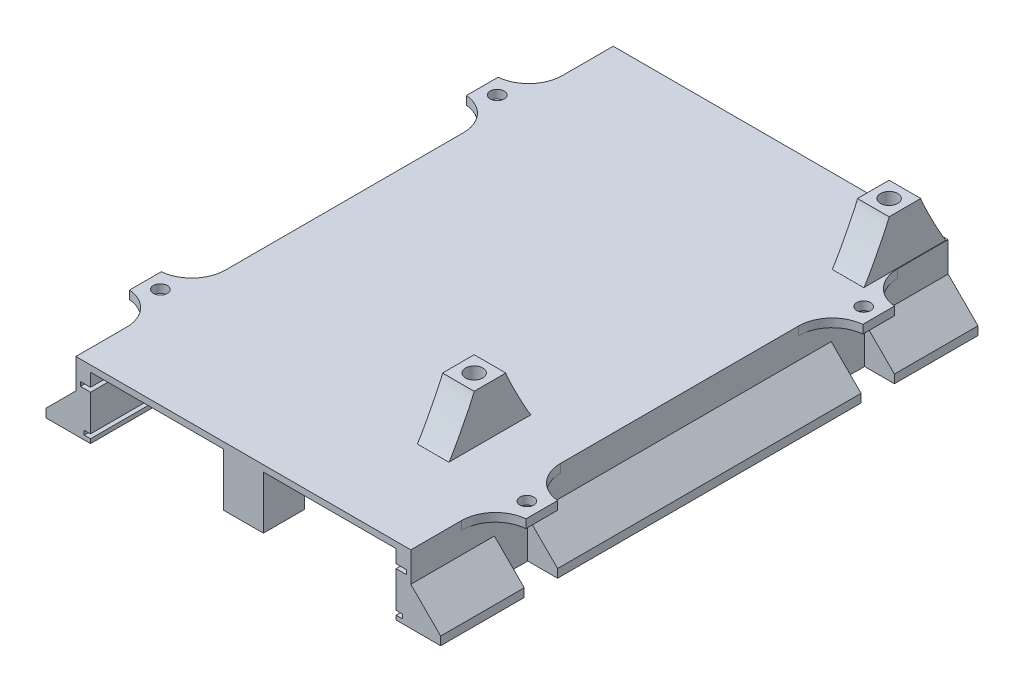
SolidWorks part; units mm, degrees
material "PLA"
ref_plane "Спереди" through (0, 0, 0) normal (0, 0, 1) x (1, 0, 0)
ref_plane "Сверху" through (0, 0, 0) normal (0, 1, 0) x (1, 0, 0)
ref_plane "Справа" through (0, 0, 0) normal (1, 0, 0) x (0, 0, -1)
sketch "Эскиз1" plane through (0, 0, 0) normal (0, 1, 0) x (1, 0, 0)
  line L0 (0, 0) -> (-4740.9496, 0) construction
  line L1 (0, 0) -> (0, -4740.9496) construction
  line L2 (36.2, 63.65) -> (39.675, 63.65)
  line L3 (-36.2, -63.65) -> (-39.675, -63.65)
  line L4 (-36.2, -63.65) -> (-36.2, 63.65)
  line L5 (-36.2, 63.65) -> (-39.675, 63.65)
  line L6 (-39.675, -63.65) -> (-39.675, 63.65)
  line L7 (-36.2, -63.65) -> (-39.675, 63.65) construction
  line L8 (-36.2, 63.65) -> (-39.675, -63.65) construction
  line L9 (39.675, -63.65) -> (39.675, 63.65)
  line L10 (36.2, -63.65) -> (39.675, -63.65)
  line L11 (36.2, -63.65) -> (36.2, 63.65)
  line L12 (36.2, 63.65) -> (39.675, -63.65) construction
  line L13 (36.2, -63.65) -> (39.675, 63.65) construction
  point P5 (-37.9375, 0)
  point P14 (37.9375, 0)
  dimension "D2" = 127.3
  dimension "D3" = 72.4
  dimension "D4" = 79.35
extrude "Бобышка-Вытянуть1" add sketch "Эскиз1" along normal blind 12.65
sketch "Эскиз2" plane through (0, 12.65, 0) normal (0, 1, 0) x (1, 0, 0)
  line L1 (39.675, 63.65) -> (-39.675, 63.65)
  line L2 (39.675, 63.65) -> (39.675, -63.65)
  line L3 (39.675, -63.65) -> (-39.675, -63.65)
  line L4 (-39.675, 63.65) -> (-39.675, -63.65)
extrude "Бобышка-Вытянуть2" add sketch "Эскиз2" along normal blind 1.5
sketch "Эскиз3" plane through (0, 0, -63.65) normal (0, 0, -1) x (-1, 0, 0)
  line L0 (0, 0) -> (0, 50000) construction
  line L1 (-36.2, 12.65) -> (-36.2, 0) construction
  line L2 (-36.2, 9.55) -> (-38.6, 9.55)
  line L3 (-36.2, 9.55) -> (-36.2, 8.55)
  line L4 (-36.2, 8.55) -> (-38.6, 8.55)
  line L5 (-38.6, 9.55) -> (-38.6, 8.55)
  line L6 (36.2, 8.55) -> (38.6, 8.55)
  line L7 (38.6, 9.55) -> (38.6, 8.55)
  line L8 (36.2, 9.55) -> (38.6, 9.55)
  line L9 (36.2, 9.55) -> (36.2, 8.55)
  line L10 (-39.675, 0) -> (-36.2, 0) construction
  dimension "D1" = 2.4
  dimension "D2" = 1
  dimension "D3" = 8.55
extrude "Вырез-Вытянуть1" cut sketch "Эскиз3" against normal through all from offset 1.5 offset against normal yes
sketch "Эскиз4" plane through (0, 12.65, 0) normal (0, -1, 0) x (1, 0, 0)
  line L0 (36.2, -63.65) -> (36.2, 63.65) construction
  line L1 (-36.2, -63.65) -> (36.2, -63.65)
  line L2 (-36.2, -63.65) -> (-36.2, -62.15)
  line L3 (-36.2, -62.15) -> (36.2, -62.15)
  line L4 (36.2, -63.65) -> (36.2, -62.15)
  dimension "D1" = 1.5
extrude "Бобышка-Вытянуть3" add sketch "Эскиз4" along normal up to surface (12.65 mm away) up to face at (37.9375, 0, 0)
sketch "Эскиз6" plane through (0, 12.65, 0) normal (0, -1, 0) x (1, 0, 0)
  line L0 (36.2, -62.15) -> (36.2, 63.65) construction
  line L1 (32.85, -52.35) -> (25.35, -52.35)
  line L2 (32.85, -52.35) -> (32.85, -62.15)
  line L3 (32.85, -59.85) -> (25.35, -59.85) construction
  line L4 (25.35, -52.35) -> (25.35, -62.15)
  line L5 (32.85, -52.35) -> (25.35, -59.85) construction
  line L6 (32.85, -59.85) -> (25.35, -52.35) construction
  line L7 (36.2, -62.15) -> (-36.2, -62.15) construction
  line L8 (32.85, -62.15) -> (25.35, -62.15)
  circle A0 centre (29.1, -56.1) radius 2.1 construction
  point P0 (29.1, -56.1)
  dimension "D3" = 4.2
  dimension "D4" = 1.65
  dimension "D5" = 1.65
  dimension "D1" = 7.1
  dimension "D2" = 6.05
extrude "Бобышка-Вытянуть5" add sketch "Эскиз6" along normal blind 9.6
sketch "Эскиз7" plane through (0, 3.05, 0) normal (0, -1, 0) x (1, 0, 0)
  line L0 (25.35, -52.35) -> (32.85, -59.85) construction
  line L1 (32.85, -52.35) -> (25.35, -59.85) construction
  line L2 (32.85, -62.15) -> (32.85, -52.35) construction
  line L3 (25.35, -52.35) -> (25.35, -62.15) construction
  circle A0 centre (29.1, -56.1) radius 2.05
  dimension "D1" = 4.1
extrude "Вырез-Вытянуть2" cut sketch "Эскиз7" against normal blind 4.5
sketch "Эскиз8" plane through (0, 0, 0) normal (0, -1, 0) x (1, 0, 0)
  line L0 (-36.2, 63.65) -> (-36.2, -62.15) construction
  line L1 (-36.2, 36.4) -> (-38.6, 36.4)
  line L2 (-36.2, 36.4) -> (-36.2, 30.55)
  line L3 (-36.2, 30.55) -> (-38.6, 30.55)
  line L4 (-38.6, 36.4) -> (-38.6, 30.55)
  line L5 (0, 0) -> (0, 50000) construction
  line L6 (-36.2, -18.2) -> (-38.6, -18.2)
  line L7 (-36.2, -18.2) -> (-36.2, -24.05)
  line L8 (-36.2, -24.05) -> (-38.6, -24.05)
  line L9 (-38.6, -18.2) -> (-38.6, -24.05)
  line L10 (-39.675, 63.65) -> (-36.2, 63.65) construction
  line L11 (36.2, -24.05) -> (38.6, -24.05)
  line L12 (38.6, -18.2) -> (38.6, -24.05)
  line L13 (36.2, -18.2) -> (38.6, -18.2)
  line L14 (36.2, -18.2) -> (36.2, -24.05)
  line L15 (36.2, 30.55) -> (38.6, 30.55)
  line L16 (38.6, 36.4) -> (38.6, 30.55)
  line L17 (36.2, 36.4) -> (38.6, 36.4)
  line L18 (36.2, 36.4) -> (36.2, 30.55)
  line L19 (39.675, -63.65) -> (-39.675, -63.65) construction
  point P26 (0, -63.65)
  dimension "D1" = 2.4
  dimension "D2" = 5.85
  dimension "D3" = 48.75
  dimension "D4" = 27.25
extrude "Вырез-Вытянуть3" cut sketch "Эскиз8" against normal up to surface (8.55 mm away) up to face at (-37.4, 8.55, 0.75)
sketch "Эскиз10" plane through (0, 12.65, 0) normal (0, -1, 0) x (1, 0, 0)
  line L0 (-36.2, 63.65) -> (-36.2, -62.15) construction
  line L1 (-25.8, -51.75) -> (-28.8, -51.75)
  line L2 (-25.8, -51.75) -> (-25.8, -57.7)
  line L3 (-25.8, -57.7) -> (-28.8, -57.7)
  line L4 (-28.8, -51.75) -> (-28.8, -57.7)
  line L5 (25.35, -62.15) -> (-36.2, -62.15) construction
  line L6 (36.2, -62.15) -> (-36.2, -62.15) construction
  line L8 (14.7, -51.75) -> (17.7, -51.75)
  line L9 (14.7, -51.75) -> (14.7, -57.7)
  line L10 (14.7, -57.7) -> (17.7, -57.7)
  line L11 (17.7, -51.75) -> (17.7, -57.7)
  dimension "D1" = 10.4
  dimension "D2" = 4.45
  dimension "D3" = 10.4
  dimension "D4" = 3
  dimension "D5" = 50.9
extrude "Бобышка-Вытянуть6" add sketch "Эскиз10" along normal blind 3.95
sketch "Эскиз11" plane through (0, 12.65, 0) normal (0, -1, 0) x (1, 0, 0)
  line L1 (-25.8, -57.7) -> (14.7, -57.7)
  line L2 (-25.8, -57.7) -> (-25.8, -51.75)
  line L3 (-25.8, -51.75) -> (14.7, -51.75)
  line L4 (14.7, -57.7) -> (14.7, -51.75)
extrude "Бобышка-Вытянуть7" add sketch "Эскиз11" along normal blind 0.35
fillet "Скругление4" radius 4 1 edges at (-5.55, 12.65, -57.7)
fillet "Скругление5" radius 2 2 edges at (-27.3, 8.7, -57.7) (16.2, 8.7, -57.7)
sketch "Эскиз12" plane through (0, 0, -62.15) normal (0, 0, 1) x (1, 0, 0)
  line L1 (15.95, 6.65) -> (-27.05, 6.65)
  line L2 (15.95, 6.65) -> (15.95, 11.65)
  line L7 (25.35, 12.65) -> (-36.2, 12.65) construction
  line L12 (15.95, 11.65) -> (-27.05, 11.65)
  line L13 (-27.05, 6.65) -> (-27.05, 11.65)
  line L15 (-5.55, 12.3) -> (-5.55, 11.65) construction
  line L17 (-25.8, 12.3) -> (14.7, 12.3) construction
  point P13 (-5.55, 12.3)
  dimension "D1" = 5
  dimension "D2" = 43
  dimension "D3" = 1
extrude "Вырез-Вытянуть4" cut sketch "Эскиз12" against normal through all
sketch "Эскиз13" plane through (0, 12.65, 0) normal (0, -1, 0) x (1, 0, 0)
  line L0 (0, 63.65) -> (0, 50063.65) construction
  line L1 (-36.2, 63.65) -> (36.2, 63.65) construction
  line L2 (-4.75, 63.4) -> (-4.75, 63.65)
  line L3 (4.75, 63.4) -> (-4.75, 63.4) construction
  line L4 (4.75, 63.4) -> (4.75, 53.9)
  line L5 (4.75, 53.9) -> (-4.75, 53.9)
  line L6 (-4.75, 63.4) -> (-4.75, 53.9)
  line L7 (4.75, 63.4) -> (-4.75, 53.9) construction
  line L8 (4.75, 53.9) -> (-4.75, 63.4) construction
  line L9 (-4.75, 63.65) -> (4.75, 63.65)
  line L10 (4.75, 63.65) -> (4.75, 63.4)
  circle A0 centre (0, 58.65) radius 2.75 construction
  point P4 (0, 63.65)
  point P5 (0, 58.65)
  dimension "D1" = 5.5
  dimension "D2" = 9.5
  dimension "D3" = 5
  dimension "D4" = 0.25
extrude "Бобышка-Вытянуть8" add sketch "Эскиз13" along normal blind 12.55
sketch "Эскиз14" plane through (0, 0.1, 0) normal (0, -1, 0) x (1, 0, 0)
  line L0 (-4.75, 63.4) -> (4.75, 53.9) construction
  line L1 (4.75, 63.4) -> (-4.75, 53.9) construction
  line L2 (4.75, 53.9) -> (4.75, 63.65) construction
  line L3 (-4.75, 63.65) -> (-4.75, 53.9) construction
  line L4 (-4.75, 63.4) -> (4.75, 63.4) construction
  circle A0 centre (0, 58.65) radius 2.05
  dimension "D1" = 4.1
extrude "Вырез-Вытянуть5" cut sketch "Эскиз14" against normal blind 7
sketch "Эскиз15" plane through (0, 14.15, 0) normal (0, 1, 0) x (1, 0, 0)
  line L0 (39.675, -63.65) -> (39.675, 63.65) construction
  line L1 (32.0454, 57.2971) -> (39.5454, 57.2971)
  line L2 (32.0454, 57.2971) -> (32.0454, 49.7971)
  line L3 (32.0454, 49.7971) -> (39.5454, 49.7971)
  line L4 (39.5454, 57.2971) -> (39.5454, 49.7971)
  line L5 (32.0454, 57.2971) -> (39.5454, 49.7971) construction
  line L6 (32.0454, 49.7971) -> (39.5454, 57.2971) construction
  line L7 (18.7005, -27.6612) -> (26.2005, -27.6612)
  line L8 (18.7005, -27.6612) -> (18.7005, -35.1612)
  line L9 (18.7005, -35.1612) -> (26.2005, -35.1612)
  line L10 (26.2005, -27.6612) -> (26.2005, -35.1612)
  line L11 (18.7005, -27.6612) -> (26.2005, -35.1612) construction
  line L12 (18.7005, -35.1612) -> (26.2005, -27.6612) construction
  line L13 (-39.675, -63.65) -> (39.675, -63.65) construction
  point P0 (35.7954, 53.5471)
  point P5 (22.4505, -31.4112)
  dimension "D1" = 7.5
  dimension "D2" = 17.2245
  dimension "D3" = 32.2388
  dimension "D4" = 3.8796
  dimension "D5" = 117.1971
extrude "Бобышка-Вытянуть9" add sketch "Эскиз15" along normal blind 11.55
sketch "Эскиз16" plane through (0, 25.7, 0) normal (0, 1, 0) x (1, 0, 0)
  line L0 (32.0454, 57.2971) -> (39.5454, 49.7971) construction
  line L1 (39.5454, 57.2971) -> (32.0454, 49.7971) construction
  line L2 (26.2005, -27.6612) -> (18.7005, -35.1612) construction
  line L3 (18.7005, -27.6612) -> (26.2005, -35.1612) construction
  circle A0 centre (22.4505, -31.4112) radius 2.05
  circle A1 centre (35.7954, 53.5471) radius 2.05
  dimension "D1" = 4.1
extrude "Вырез-Вытянуть6" cut sketch "Эскиз16" against normal blind 5
sketch "Эскиз17" plane through (0, 0, -63.65) normal (0, 0, -1) x (-1, 0, 0)
  line L0 (-39.675, 7.075) -> (-46.75, 0)
  line L1 (-39.675, 14.15) -> (-39.675, 0) construction
  line L2 (-46.75, 0) -> (-39.675, 0)
  line L3 (-39.675, 0) -> (-39.675, 7.075)
  line L4 (0, 0) -> (0, 50000) construction
  line L5 (46.75, 0) -> (39.675, 0)
  line L6 (39.675, 7.075) -> (46.75, 0)
  line L7 (39.675, 0) -> (39.675, 7.075)
extrude "Бобышка-Вытянуть10" add sketch "Эскиз17" against normal up to surface (127.3 mm away) up to face at (0, 7.575, 63.65)
sketch "Эскиз18" plane through (0, 0, -63.65) normal (0, 0, -1) x (-1, 0, 0)
  line L0 (-46.75, 0) -> (-46.75, -2)
  line L1 (-46.75, -2) -> (-36.2, -2)
  line L2 (-36.2, -2) -> (-36.2, -1)
  line L3 (-36.2, -1) -> (-37.7, -1)
  line L4 (-37.7, -1) -> (-37.7, 0)
  line L5 (-46.75, 0) -> (46.75, 0) construction
  line L6 (-37.7, 0) -> (-46.75, 0)
  line L7 (-36.2, 8.55) -> (-36.2, 0) construction
  line L8 (0, 0) -> (0, 50000) construction
  line L9 (37.7, -1) -> (37.7, 0)
  line L10 (36.2, -1) -> (37.7, -1)
  line L11 (36.2, -2) -> (36.2, -1)
  line L12 (46.75, -2) -> (36.2, -2)
  line L13 (46.75, 0) -> (46.75, -2)
  line L14 (37.7, 0) -> (46.75, 0)
  point P21 (0, 0)
  dimension "D1" = 2
  dimension "D2" = 1
  dimension "D3" = 1.5
extrude "Бобышка-Вытянуть11" add sketch "Эскиз18" against normal up to surface (127.3 mm away) up to face at (0, 7.5295, 63.65)
sketch "Эскиз19" plane through (0, 14.15, 0) normal (0, 1, 0) x (1, 0, 0)
  line L0 (-39.675, -63.65) -> (-46.75, -63.65) construction
  line L1 (-49.0446, -29.2779) -> (-41.5446, -29.2779) construction
  line L2 (-49.0446, -29.2779) -> (-49.0446, -21.7779) construction
  line L3 (-49.0446, -21.7779) -> (-41.5446, -21.7779) construction
  line L4 (-41.5446, -29.2779) -> (-41.5446, -21.7779) construction
  line L5 (-39.675, 63.65) -> (-39.675, -63.65) construction
  line L6 (-49.2446, -29.4779) -> (-41.3446, -29.4779)
  line L7 (-41.3446, -29.4779) -> (-41.3446, -21.5779)
  line L8 (-49.2446, -21.5779) -> (-41.3446, -21.5779)
  line L9 (-49.2446, -29.4779) -> (-49.2446, -21.5779)
  dimension "D1" = 34.3721
  dimension "D2" = 7.5
  dimension "D3" = 1.8696
  dimension "D4" = 0.2
extrude "Вырез-Вытянуть7" cut sketch "Эскиз19" against normal up to surface (16.15 mm away) up to face at (-41.475, -2, 0)
sketch "Эскиз20" plane through (0, -2, 0) normal (0, -1, 0) x (1, 0, 0)
  line L0 (0, 0) -> (0, 50000) construction
  line L1 (0, 0) -> (50000, 0) construction
  line L3 (39.875, 43.65) -> (47.375, 43.65) construction
  line L4 (39.875, 43.65) -> (39.875, 36.15) construction
  line L5 (39.875, 36.15) -> (47.375, 36.15) construction
  line L6 (47.375, 43.65) -> (47.375, 36.15) construction
  line L7 (36.2, 63.65) -> (46.75, 63.65) construction
  line L20 (39.675, 43.85) -> (47.575, 43.85)
  line L21 (47.575, 43.85) -> (47.575, 35.95)
  line L22 (39.675, 35.95) -> (47.575, 35.95)
  line L23 (39.675, 43.85) -> (39.675, 35.95)
  line L24 (39.675, -43.85) -> (39.675, -35.95)
  line L25 (39.675, -35.95) -> (47.575, -35.95)
  line L26 (47.575, -43.85) -> (47.575, -35.95)
  line L27 (39.675, -43.85) -> (47.575, -43.85)
  line L28 (-39.675, -43.85) -> (-47.575, -43.85)
  line L29 (-47.575, -43.85) -> (-47.575, -35.95)
  line L30 (-39.675, -35.95) -> (-47.575, -35.95)
  line L31 (-39.675, -43.85) -> (-39.675, -35.95)
  line L32 (-39.675, 43.85) -> (-39.675, 35.95)
  line L33 (-39.675, 35.95) -> (-47.575, 35.95)
  line L34 (-47.575, 43.85) -> (-47.575, 35.95)
  line L35 (-39.675, 43.85) -> (-47.575, 43.85)
  line L38 (39.675, 63.65) -> (39.675, -63.65) construction
  dimension "D1" = 7.5
  dimension "D2" = 20
  dimension "D3" = 0.2
extrude "Вырез-Вытянуть8" cut sketch "Эскиз20" against normal through all
sketch "Эскиз21" plane through (0, 14.15, 0) normal (0, 1, 0) x (1, 0, 0)
  line L0 (0, 0) -> (-50000, 0) construction
  line L1 (0, 0) -> (0, 50000) construction
  line L2 (39.675, -63.65) -> (39.675, 63.65) construction
  line L3 (39.675, 43.65) -> (46.95, 43.65)
  line L4 (39.675, 43.65) -> (39.675, 36.15)
  line L5 (39.675, 36.15) -> (46.95, 36.15)
  line L6 (46.95, 43.65) -> (46.95, 36.15)
  line L7 (46.75, 43.85) -> (39.675, 43.85) construction
  line L8 (39.675, 35.95) -> (46.75, 35.95) construction
  line L10 (39.675, -36.15) -> (46.95, -36.15)
  line L11 (46.95, -43.65) -> (46.95, -36.15)
  line L12 (39.675, -43.65) -> (46.95, -43.65)
  line L13 (39.675, -43.65) -> (39.675, -36.15)
  line L14 (-39.675, -43.65) -> (-39.675, -36.15)
  line L15 (-39.675, -43.65) -> (-46.95, -43.65)
  line L16 (-46.95, -43.65) -> (-46.95, -36.15)
  line L17 (-39.675, -36.15) -> (-46.95, -36.15)
  line L18 (-39.675, 36.15) -> (-46.95, 36.15)
  line L19 (-46.95, 43.65) -> (-46.95, 36.15)
  line L20 (-39.675, 43.65) -> (-46.95, 43.65)
  line L21 (-39.675, 43.65) -> (-39.675, 36.15)
  line L22 (46.75, 43.85) -> (46.75, 63.65) construction
  dimension "D1" = 0.2
  dimension "D2" = 0.2
  dimension "D3" = 0.2
extrude "Бобышка-Вытянуть12" add sketch "Эскиз21" against normal blind 2
sketch "Эскиз22" plane through (0, 14.15, 0) normal (0, 1, 0) x (1, 0, 0)
  line L0 (39.875, 43.65) -> (39.875, 36.15) construction
  line L1 (46.95, 43.65) -> (39.675, 43.65) construction
  line L2 (39.675, 36.15) -> (46.95, 36.15) construction
  line L3 (39.675, 43.65) -> (39.675, 63.65) construction
  line L4 (39.875, 43.65) -> (46.95, 36.15) construction
  line L5 (46.95, 43.65) -> (39.875, 36.15) construction
  line L6 (0, 0) -> (-50000, 0) construction
  line L7 (0, 0) -> (0, -50000) construction
  circle A0 centre (43.4125, 39.9) radius 1.65
  circle A1 centre (43.4125, -39.9) radius 1.65
  circle A2 centre (-43.4125, -39.9) radius 1.65
  circle A3 centre (-43.4125, 39.9) radius 1.65
  dimension "D2" = 3.3
  dimension "D1" = 0.2
extrude "Вырез-Вытянуть9" cut sketch "Эскиз22" against normal up to surface (2 mm away) up to face at (-43.3125, 12.15, -39.9)
fillet "Скругление6" radius 6 4 edges at (35.7954, 14.15, -57.2971) (35.7954, 14.15, -49.7971) (22.4505, 14.15, 27.6612) (22.4505, 14.15, 35.1612) second distance 11.55 conic rho 0.05 first distance on face at (-43.4125, 14.15, -41.55)
fillet "Скругление7" radius 8 8 edges at (39.675, 13.15, 36.15) (39.675, 13.15, 43.65) (39.675, 13.15, -36.15) (39.675, 13.15, -43.65) (-39.675, 13.15, -43.65) (-39.675, 13.15, -36.15) (-39.675, 13.15, 36.15) (-39.675, 13.15, 43.65)
